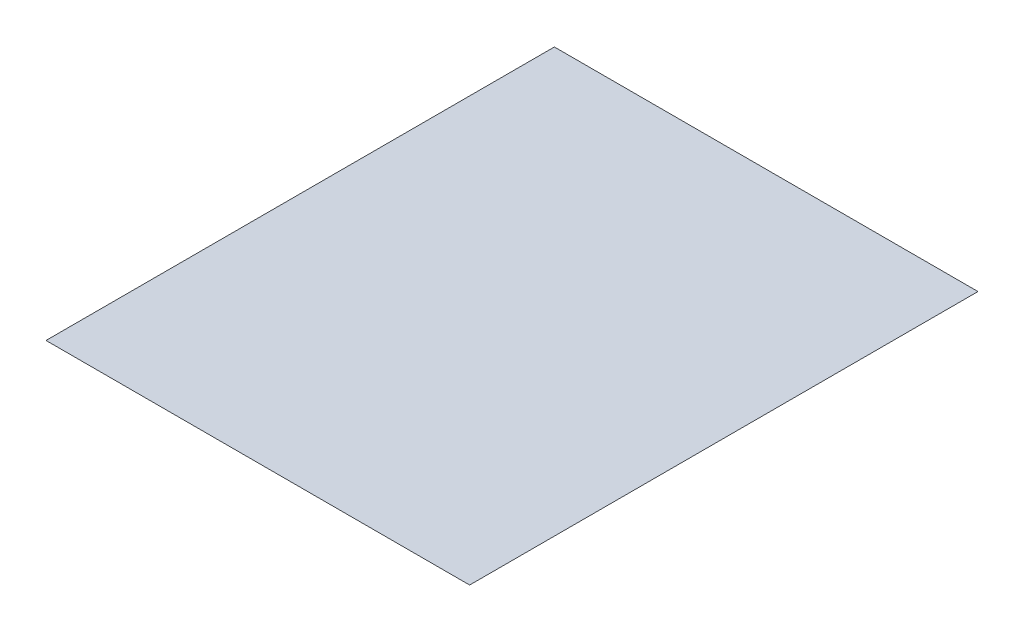
SolidWorks part; units mm, degrees
ref_plane "Front Plane" through (0, 0, 0) normal (0, 0, 1) x (1, 0, 0)
ref_plane "Top Plane" through (0, 0, 0) normal (0, 1, 0) x (1, 0, 0)
ref_plane "Right Plane" through (0, 0, 0) normal (1, 0, 0) x (0, 0, -1)
sketch "Sketch1" plane through (0, 0, 0) normal (0, 0, 1) x (1, 0, 0)
  circle A1 centre (0, 180) radius 5
  arc A2 (-5, 180) -> (3.5355, 176.4645) centre (0, 180) ccw construction
extrude "Boss-Extrude1" add sketch "Sketch1" along normal mid plane 45
sketch "Sketch4" plane through (0, 0, 22.5) normal (0, 0, 1) x (1, 0, 0)
  line L0 (-20, 180) -> (-20, 205)
  line L1 (-20, 205) -> (20, 205)
  line L2 (20, 205) -> (20, 180)
  arc A0 (-20, 180) -> (20, 180) centre (0, 180) ccw
  dimension "D1" = 25
extrude "Boss-Extrude4" add sketch "Sketch4" along normal blind 10
sketch "Sketch5" plane through (0, 0, 32.5) normal (0, 0, 1) x (1, 0, 0)
  line L0 (-20, 180) -> (20, 180)
  arc A0 (-20, 180) -> (20, 180) centre (0, 180) ccw
extrude "Boss-Extrude5" add sketch "Sketch5" along normal blind 20
fillet "Fillet1" radius 20 1 edges at (0, 160, 52.5) conic radius 20
sketch "Sketch6" plane through (0, 180, 0) normal (0, 1, 0) x (1, 0, 0)
  line L0 (20, -32.5) -> (-20, -32.5) construction
  line L1 (20, -32.5) -> (-20, -32.5)
  arc A0 (-20, -32.5) -> (20, -32.5) centre (0, -32.5) ccw
extrude "Boss-Extrude6" add sketch "Sketch6" along normal blind 25
sketch "Sketch7" plane through (0, 0, -22.5) normal (0, 0, -1) x (-1, 0, 0)
  line L6 (20, 180) -> (20, 205)
  line L7 (20, 205) -> (-20, 205)
  line L8 (-20, 205) -> (-20, 180)
  line L9 (20, 180) -> (20, 205)
  line L10 (20, 205) -> (-20, 205)
  line L11 (-20, 205) -> (-20, 180)
  arc A2 (-20, 180) -> (20, 180) centre (0, 180) ccw
  arc A3 (-20, 180) -> (20, 180) centre (0, 180) ccw
  dimension "D1" = 0
extrude "Boss-Extrude7" add sketch "Sketch7" along normal blind 30
fillet "Fillet3" radius 20 3 edges at (0, 160, -52.5) (20, 192.5, -52.5) (-20, 192.5, -52.5) conic radius 20
sketch "Sketch8" plane through (0, 205, 0) normal (0, 1, 0) x (1, 0, 0)
  line L0 (0, -187.8896) -> (0, 208.6339) construction
  line L1 (100, 120) -> (-100, 120)
  line L2 (100, 120) -> (100, -120)
  line L3 (100, -120) -> (-100, -120)
  line L4 (-100, 120) -> (-100, -120)
  line L5 (134.9007, 0) -> (-180.2847, 0) construction
  dimension "D1" = 100
  dimension "D2" = 120
  dimension "D3" = 240
  dimension "D4" = 200
extrude "Boss-Extrude8" add sketch "Sketch8" along normal blind 10 contours L4 L3 L2 L1
chamfer "Chamfer1" distance 10 angle 45 4 edges at (100, 205, 0) (0, 205, -120) (-100, 205, 0) (0, 205, 120)
